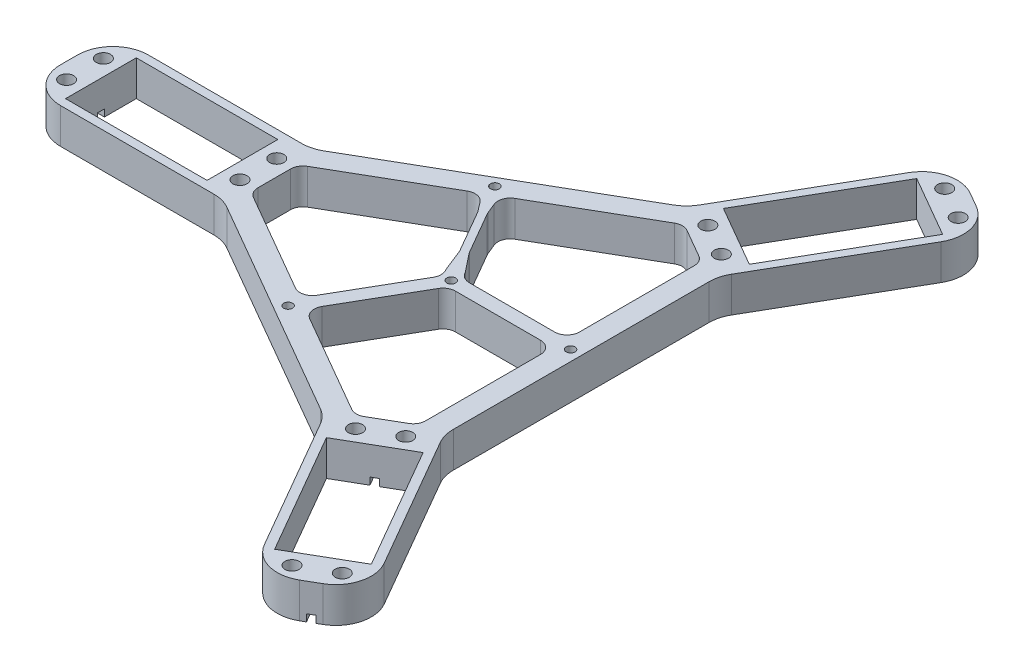
SolidWorks part; units mm, degrees
ref_plane "Front Plane" through (0, 0, 0) normal (0, 0, 1) x (1, 0, 0)
ref_plane "Top Plane" through (0, 0, 0) normal (0, 1, 0) x (1, 0, 0)
ref_plane "Right Plane" through (0, 0, 0) normal (1, 0, 0) x (0, 0, -1)
sketch "Sketch1" plane through (0, 0, 0) normal (0, 1, 0) x (1, 0, 0)
  line L0 (0, 10) -> (40, 10) construction
  line L1 (0, 0) -> (40, 0)
  line L2 (0, 0) -> (0, 20)
  line L3 (0, 20) -> (40, 20)
  line L4 (40, 0) -> (40, 20)
  line L5 (0, 20) -> (-4.5, 20)
  line L6 (-9, -2.4) -> (49, -2.4)
  line L7 (-9, -2.4) -> (-9, 22.4)
  line L8 (-9, 22.4) -> (49, 22.4)
  line L9 (49, -2.4) -> (49, 22.4)
  line L10 (-9, -2.4) -> (49, 22.4) construction
  line L11 (-9, 22.4) -> (49, -2.4) construction
  line L12 (-4.5, 20) -> (-4.5, 15.2)
  line L13 (20, 20) -> (20, 0) construction
  line L14 (49, 10) -> (130.7387, 10)
  line L15 (139.8397, 100.7365) -> (119.8397, 66.0955)
  line L16 (139.8397, 100.7365) -> (157.1603, 90.7365)
  line L17 (157.1603, 90.7365) -> (137.1603, 56.0955)
  line L18 (119.8397, 66.0955) -> (137.1603, 56.0955)
  line L19 (157.1603, 90.7365) -> (159.4103, 94.6336)
  line L20 (142.2613, 109.7307) -> (113.2613, 59.5013)
  line L21 (142.2613, 109.7307) -> (163.7387, 97.3307)
  line L22 (163.7387, 97.3307) -> (134.7387, 47.1013)
  line L23 (113.2613, 59.5013) -> (134.7387, 47.1013)
  line L24 (159.4103, 94.6336) -> (155.2533, 97.0336)
  line L25 (124, 53.3013) -> (83.1306, -17.4865)
  line L26 (148.5, 95.7365) -> (128.5, 61.0955) construction
  line L27 (142.2613, 109.7307) -> (134.7387, 47.1013) construction
  line L28 (163.7387, 97.3307) -> (113.2613, 59.5013) construction
  line L29 (147.1603, 73.416) -> (129.8397, 83.416) construction
  line L30 (157.1603, -70.7365) -> (137.1603, -36.0955)
  line L31 (157.1603, -70.7365) -> (139.8397, -80.7365)
  line L32 (139.8397, -80.7365) -> (119.8397, -46.0955)
  line L33 (137.1603, -36.0955) -> (119.8397, -46.0955)
  line L34 (139.8397, -80.7365) -> (142.0897, -84.6336)
  line L35 (163.7387, -77.3307) -> (134.7387, -27.1013)
  line L36 (163.7387, -77.3307) -> (142.2613, -89.7307)
  line L37 (142.2613, -89.7307) -> (113.2613, -39.5013)
  line L38 (134.7387, -27.1013) -> (113.2613, -39.5013)
  line L39 (142.0897, -84.6336) -> (146.2467, -82.2336)
  line L40 (124, -33.3013) -> (83.1306, 37.4865)
  line L41 (148.5, -75.7365) -> (128.5, -41.0955) construction
  line L42 (163.7387, -77.3307) -> (113.2613, -39.5013) construction
  line L43 (142.2613, -89.7307) -> (134.7387, -27.1013) construction
  line L44 (129.8397, -63.416) -> (147.1603, -53.416) construction
  line L45 (49, 22.4) -> (113.2613, 59.5013)
  line L46 (134.7387, 47.1013) -> (134.7387, -27.1013)
  line L47 (113.2613, -39.5013) -> (49, -2.4)
  line L48 (49, 17.7812) -> (117.2613, 57.1919)
  line L49 (130.7387, 49.4107) -> (130.7387, -29.4107)
  line L50 (117.2613, -37.1919) -> (49, 2.2188)
  line L51 (51, 18.9359) -> (115.2613, 56.0372) construction
  line L52 (130.7387, 47.1013) -> (130.7387, -27.1013) construction
  line L53 (115.2613, -36.0372) -> (51, 1.0641) construction
  line L54 (122.2679, 54.3013) -> (81.3986, -16.4865)
  line L55 (49, 8) -> (130.7387, 8)
  line L56 (125.7321, -32.3013) -> (99, 14)
  line L57 (125.7321, 52.3013) -> (84.8627, -18.4865)
  line L58 (49, 12) -> (130.7387, 12)
  line L59 (122.2679, -34.3013) -> (95.5359, 12)
  line L60 (49, 12) -> (99, 12) construction
  line L61 (125.7321, -32.3013) -> (100.7321, 11) construction
  line L62 (122.2679, 54.3013) -> (97.2679, 11) construction
  line L63 (122.2679, -34.3013) -> (97.2679, 9) construction
  line L64 (124, 53.3013) -> (99, 10) construction
  line L65 (125.7321, 52.3013) -> (100.7321, 9) construction
  line L66 (124, -33.3013) -> (99, 10) construction
  line L67 (49, 10) -> (99, 10) construction
  line L68 (49, 8) -> (99, 8) construction
  line L69 (83.1306, 37.4865) -> (81.1306, 40.9506) construction
  line L70 (130.7387, 10) -> (134.7387, 10) construction
  line L71 (83.1306, -17.4865) -> (81.1306, -20.9506) construction
  line L72 (47, 22.4) -> (114.2613, 61.2333)
  line L73 (135.7387, 48.8333) -> (135.7387, -28.8333)
  line L74 (129.7387, 49.988) -> (129.7387, -29.988)
  line L75 (49, 16.6265) -> (118.2613, 56.6145)
  line L76 (118.2613, -36.6145) -> (49, 3.3735)
  line L77 (114.2613, -41.2333) -> (47, -2.4)
  line L78 (112.7613, -40.3673) -> (48.5, -3.266) construction
  line L79 (117.7613, -36.3258) -> (49.5, 3.0848) construction
  line L80 (49.5, 16.9152) -> (117.7613, 56.3258) construction
  line L81 (48.5, 23.266) -> (112.7613, 60.3673) construction
  line L82 (129.7387, 49.4107) -> (129.7387, -29.4107) construction
  line L83 (135.7387, 47.1013) -> (135.7387, -27.1013) construction
  line L84 (93.0648, 18.2801) -> (85.9961, 30.5234)
  line L85 (94.7968, 19.2801) -> (87.7282, 31.5234)
  line L86 (124.866, -32.8013) -> (83.9967, 37.9865) construction
  line L87 (123.134, -33.8013) -> (82.2646, 36.9865) construction
  line L89 (85.9961, 30.5234) -> (81.3986, 36.4865)
  line L90 (87.7282, 31.5234) -> (84.8627, 38.4865)
  line L91 (93.0648, 18.2801) -> (95.5359, 12)
  line L92 (94.7968, 19.2801) -> (99, 14)
  line L94 (122.2679, -34.3013) -> (81.3986, 36.4865) construction
  line L96 (125.7321, -32.3013) -> (84.8627, 38.4865) construction
  circle A0 centre (-4.5, 15.2) radius 2
  circle A1 centre (44.5, 15.2) radius 2
  circle A2 centre (44.5, 4.8) radius 2
  circle A3 centre (-4.5, 4.8) radius 2
  circle A4 centre (155.2533, 97.0336) radius 2
  circle A5 centre (130.7533, 54.5984) radius 2
  circle A6 centre (121.7467, 59.7984) radius 2
  circle A7 centre (146.2467, 102.2336) radius 2
  circle A8 centre (146.2467, -82.2336) radius 2
  circle A9 centre (121.7467, -39.7984) radius 2
  circle A10 centre (130.7533, -34.5984) radius 2
  circle A11 centre (155.2533, -77.0336) radius 2
  circle A12 centre (82.1306, -19.2186) radius 1.25
  circle A13 centre (82.1306, 39.2186) radius 1.25
  circle A14 centre (132.7387, 10) radius 1.25
  circle A15 centre (99, 10) radius 1.25
  point P7 (20, 10)
  point P34 (138.5, 78.416)
  point P57 (138.5, -58.416)
  point P74 (99, 10)
  dimension "D7" = 4
  dimension "D8" = 1
  dimension "D1" = 40
  dimension "D2" = 20
  dimension "D3" = 58
  dimension "D4" = 24.8
  dimension "D5" = 4.5
  dimension "D6" = 4.8
  dimension "D10" = 4
  dimension "D11" = 4
  dimension "D12" = 4
  dimension "D13" = 2
  dimension "D14" = 2
  dimension "D15" = 1
  dimension "D16" = 1
  dimension "D17" = 1
  dimension "D18" = 1
  dimension "D19" = 1
  dimension "D20" = 1
  dimension "D21" = 1
  dimension "D9" = 3
extrude "Boss-Extrude1" add sketch "Sketch1" along normal blind 10 contours L55 L54 L50 L25 | L57 L59 L25 L50 | L38 L50 L9 L47 | L59 L25 L14 | L55 L59 L54 | L40 L54 L14 | L58 L40 L25 | L54 L58 L56 | L58 L56 L57 | L14 L56 L25 | L57 L14 L40 | L25 L55 L40 | L59 L57 L55 | L56 L57 L55 | L58 L57 L14 L49 | L56 L55 L49 L14 | L59 L54 L58 | L23 L49 L38 L46 | L9 L48 L23 L45 | L6 L9 L8 L7 A1 A0 L3 L4 L1 L2 A2 A3 | L20 L23 L22 L21 A5 A4 L17 L18 L15 L16 A6 A7 | L35 L38 L37 L36 A9 A8 L32 L33 L30 L31 A10 A11 | L72 L8 L45 L20 | L9 L75 L59 L48 | L59 L75 L40 L48 | L40 L75 L56 L48 | L56 L75 L23 L48 | L73 L22 L46 L35 | L23 L74 L58 L49 | L58 L74 L14 L49 | L14 L74 L55 L49 | L55 L74 L38 L49 | L77 L37 L47 L6 | L38 L76 L57 L50 | L57 L76 L25 L50 | L25 L76 L54 L50 | L54 L76 L9 L50 | L75 L59 L58 L40 | L75 L40 L54 L56 region at (-8.3692, 0, -10) region at (80.8787, 0, 21.3869) region at (49.8, 0, 0.0906) region at (114.4579, 0, 39.9651) region at (80.8787, 0, -41.3869) region at (65.3246, 0, 6.6274) region at (81.1706, 0, -40.8814) region at (128.9579, 0, -85.0798) region at (82.5146, 0, 16.5535) region at (101.4379, 0, 27.4774) region at (65.3538, 0, -26.6439) region at (89.7346, 0, 4.062) region at (84.2467, 0, 17.5535) region at (135.2425, 0, -10) region at (82.5404, 0, -36.5751) region at (101.4091, 0, -47.4604) region at (96.6906, 0, -8.6667) region at (91.4547, 0, 5.0551) region at (132.3441, 0, 27.5725) region at (90.2068, 0, -23.9306) region at (84.2151, 0, -37.542) region at (97.5899, 0, -10.8141) region at (96.6906, 0, -11.3333) region at (97.5899, 0, -9.1859) region at (99, 0, -8.3718) region at (99, 0, -7.3333) region at (130.2374, 0, 10.85) region at (91.3324, 0, -24.5804) region at (99, 0, -11.6282) region at (99, 0, -12.6667) region at (101.3094, 0, -8.6667) region at (100.4101, 0, -9.1859) region at (130.2387, 0, -9) region at (130.2374, 0, -30.85) region at (100.4101, 0, -10.8141) region at (101.3094, 0, -11.3333) region at (115.8107, 0, -9.0069) region at (115.8107, 0, -10.9931) region at (130.2387, 0, -11)
sketch "Sketch2" plane through (-9, 0, 0) normal (-1, 0, 0) x (0, 0, 1)
  line L0 (2.4, 0) -> (-22.4, 0) construction
  line L1 (-9, -2) -> (-11, -2)
  line L2 (-9, -2) -> (-9, 2)
  line L3 (-9, 2) -> (-11, 2)
  line L4 (-11, -2) -> (-11, 2)
  line L5 (-9, -2) -> (-11, 2) construction
  line L6 (-9, 2) -> (-11, -2) construction
  point P0 (-10, 0)
  dimension "D1" = 4
  dimension "D2" = 2
extrude "Cut-Extrude1" cut sketch "Sketch2" against normal blind 56
pattern_circular "CirPattern1" count 3 every 120 about axis through (99, 0, -10) along (0, 1, 0) of "Cut-Extrude1"
fillet "Fillet1" radius 10 12 edges at (142.2613, 5, -109.7307) (163.7387, 5, -97.3307) (163.7387, 5, 77.3307) (142.2613, 5, 89.7307) (-9, 5, -22.4) (-9, 5, 2.4) (47, 5, -22.4) (114.2613, 5, -61.2333) (135.7387, 5, -48.8333) (135.7387, 5, 28.8333) (114.2613, 5, 41.2333) (47, 5, 2.4)
fillet "Fillet2" radius 3.5 21 edges at (129.7387, 5, -8) (129.7387, 5, 29.988) (118.2613, 5, 36.6145) (85.3627, 5, 17.6205) (129.7387, 5, -12) (129.7387, 5, -49.988) (118.2613, 5, -56.6145) (49, 5, -3.3735) (81.8986, 5, 15.6205) (85.2467, 5, -37.5535) (87.7282, 5, -31.5234) (94.7968, 5, -19.2801) (99, 5, -14) (100.1547, 5, -12) (96.6906, 5, -10) (95.5359, 5, -12) (93.0648, 5, -18.2801) (85.9961, 5, -30.5234) (82.0146, 5, -35.6875) (49, 5, -16.6265) (100.1547, 5, -8)
